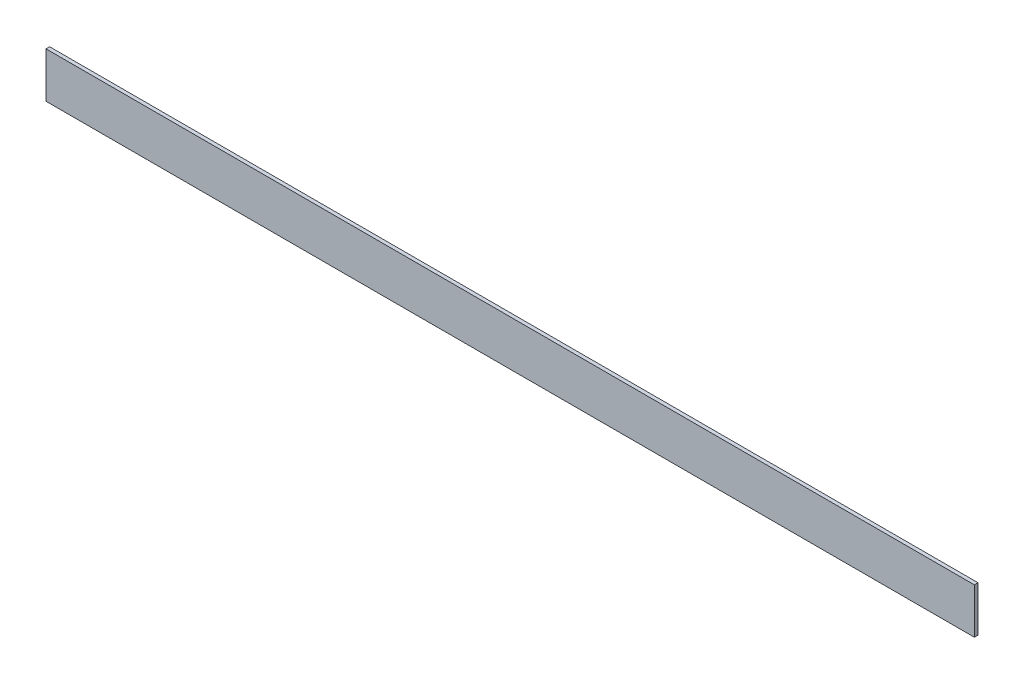
SolidWorks part; units mm, degrees
ref_plane "Спереди" through (0, 0, 0) normal (0, 0, 1) x (1, 0, 0)
ref_plane "Сверху" through (0, 0, 0) normal (0, 1, 0) x (1, 0, 0)
ref_plane "Справа" through (0, 0, 0) normal (1, 0, 0) x (0, 0, -1)
sketch "Эскиз1" plane through (0, 0, 0) normal (1, 0, 0) x (0, 0, -1)
  line L0 (0, 25) -> (0, 0)
  line L1 (0, 0) -> (25, 0)
extrude "Вытянуть-Тонкостенный1" add sketch "Эскиз1" along normal blind 511 thin thin type one direction reverse wall 2
sketch "Эскиз2" plane through (0, 0, 0) normal (0, -1, 0) x (1, 0, 0)
  line L1 (0, -2) -> (23, -2)
  line L2 (0, -2) -> (0, -25)
  line L3 (0, -25) -> (23, -25)
  line L4 (23, -2) -> (23, -25)
  line L6 (255.5, -37.238) -> (255.5, 15.2028) construction
  line L7 (488, -2) -> (488, -25)
  line L8 (511, -25) -> (488, -25)
  line L9 (511, -2) -> (511, -25)
  line L10 (511, -2) -> (488, -2)
  dimension "D1" = 23
extrude "Вырез-Вытянуть1" cut sketch "Эскиз2" against normal through all
